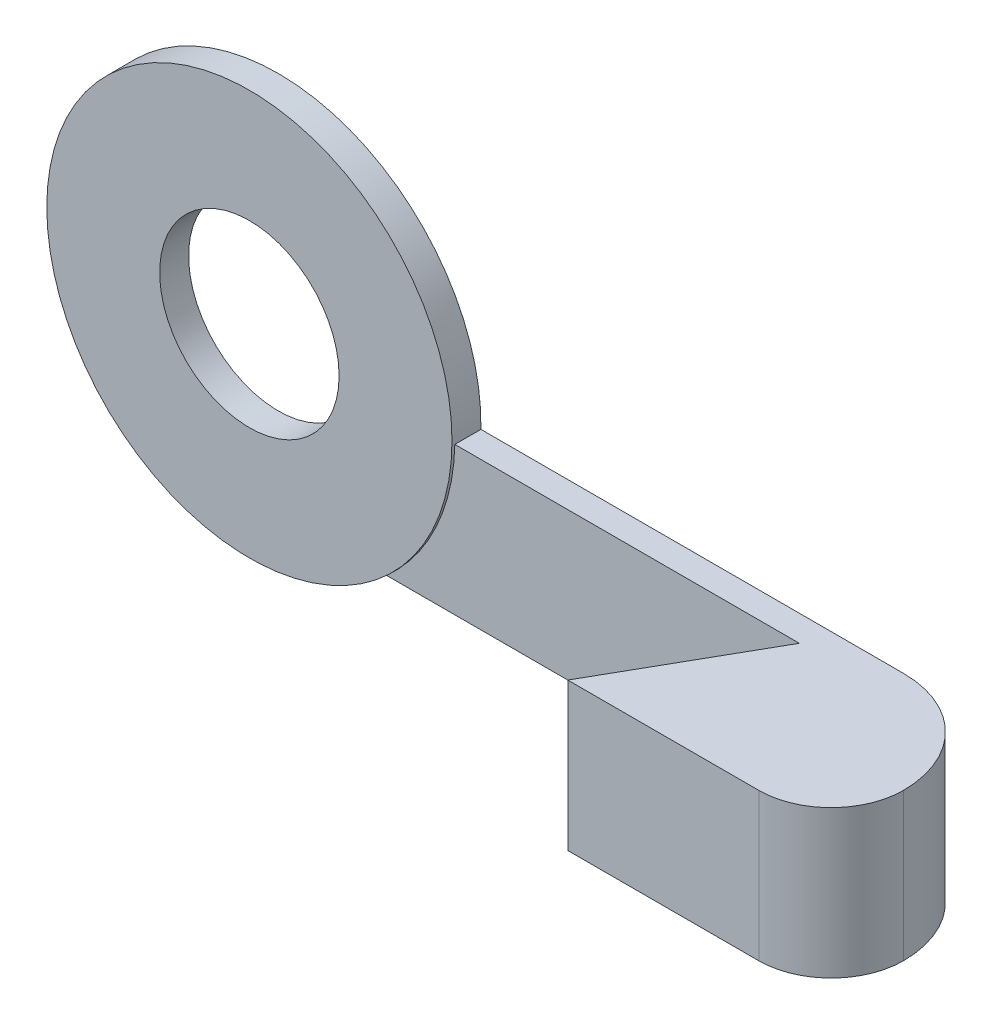
SolidWorks part; units mm, degrees
ref_plane "Front" through (0, 0, 0) normal (0, 0, 1) x (1, 0, 0)
ref_plane "Top" through (0, 0, 0) normal (0, 1, 0) x (1, 0, 0)
ref_plane "Right" through (0, 0, 0) normal (1, 0, 0) x (0, 0, -1)
sketch "Sketch3" plane through (0, 0, 0) normal (0, 1, 0) x (1, 0, 0)
  line L0 (0, -2.5) -> (-3.7, -2.5)
  line L1 (-3.7, -2.5) -> (-3.7, 3.5)
  line L2 (-3.7, 3.5) -> (-1, 3.5)
  arc A0 (2.5, 0) -> (0, -2.5) centre (0, 0) cw
  arc A1 (-1, 3.5) -> (2.5, 0) centre (-1, 0) cw
  dimension "D1" = 2.5
  dimension "D2" = 6.2
  dimension "D3" = 6
extrude "Boss-Extrude1" add sketch "Sketch3" along normal blind 5.1
sketch "Sketch4" plane through (-3.7, 0, 0) normal (-1, 0, 0) x (0, 0, 1)
  line L1 (-3.5, 5.1) -> (-2.6, 5.1)
  line L2 (-3.5, 5.1) -> (-3.5, 0)
  line L3 (-3.5, 0) -> (-2.6, 0)
  line L4 (-2.6, 5.1) -> (-2.6, 0)
  dimension "D1" = 0.9
extrude "Boss-Extrude2" add sketch "Sketch4" along normal blind 18.9
sketch "Sketch5" plane through (0, 0, -3.5) normal (0, 0, -1) x (-1, 0, 0)
  line L0 (22.6, 5.1) -> (22.6, 0) construction
  line L2 (1, 5.1) -> (22.6, 5.1) construction
  circle A0 centre (22.6, 5.25) radius 7
  dimension "D2" = 14
  dimension "D1" = 0.15
extrude "Boss-Extrude3" add sketch "Sketch5" against normal blind 1
sketch "Sketch6" plane through (0, 0, -2.6) normal (0, 0, 1) x (1, 0, 0)
  circle A0 centre (-22.6, 5.25) radius 3.1
  circle A1 centre (-22.6, 5.25) radius 7 construction
  dimension "D1" = 6.2
extrude "Cut-Extrude1" cut sketch "Sketch6" against normal through all both and the other way through all
sketch "Sketch7" plane through (0, 0, 0) normal (0, -1, 0) x (1, 0, 0)
  line L3 (-3.7, -2.6) -> (-3.7, 2.5)
  line L4 (-3.7, 2.5) -> (-6.6, 2.5)
  line L5 (-6.6, 2.5) -> (-3.7, -2.6)
  dimension "D1" = 2.9
extrude "Boss-Extrude4" add sketch "Sketch7" against normal up to surface (5.1 mm away) up to face at (-5.1229, 5.1, -1.0582)
